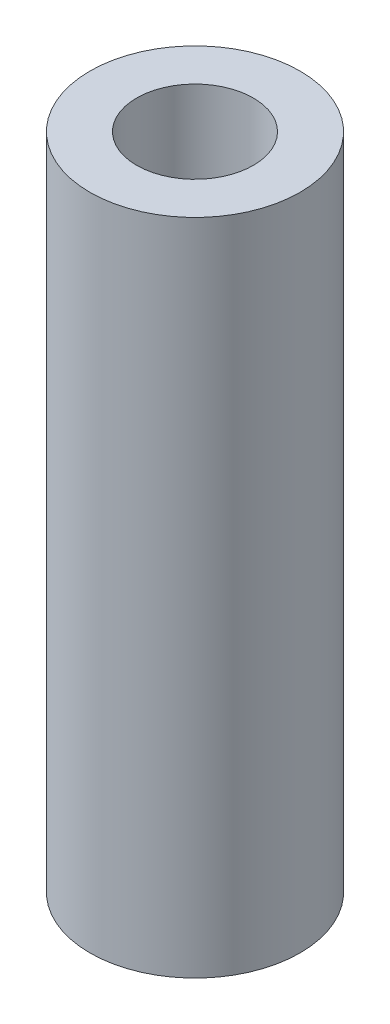
SolidWorks part; units mm, degrees
material "EPDM"
ref_plane "Płaszczyzna przednia" through (0, 0, 0) normal (0, 0, 1) x (1, 0, 0)
ref_plane "Płaszczyzna górna" through (0, 0, 0) normal (0, 1, 0) x (1, 0, 0)
ref_plane "Płaszczyzna prawa" through (0, 0, 0) normal (1, 0, 0) x (0, 0, -1)
sketch "Szkic1" plane through (0, 0, 0) normal (0, 0, 1) x (1, 0, 0)
  line L0 (0, 344.7443) -> (0, -336.9732) construction
  line L1 (35, 197.5) -> (63, 197.5)
  line L2 (35, 197.5) -> (35, -197.5)
  line L3 (35, -197.5) -> (63, -197.5)
  line L4 (63, 197.5) -> (63, -197.5)
  point P4 (35, 0)
  dimension "D1" = 63
  dimension "D2" = 35
  dimension "D3" = 395
revolve "Obrót1" add sketch "Szkic1" angle 360 about L0
